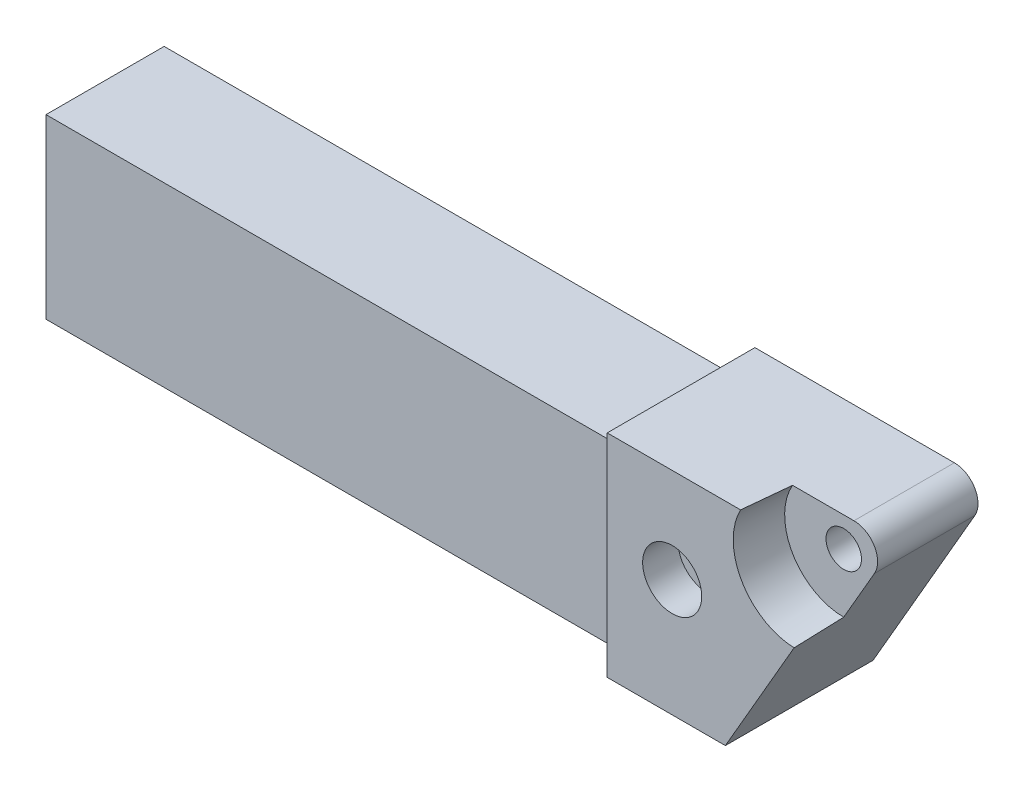
SolidWorks part; units mm, degrees
ref_plane "前视基准面" through (0, 0, 0) normal (0, 0, 1) x (1, 0, 0)
ref_plane "上视基准面" through (0, 0, 0) normal (0, 1, 0) x (1, 0, 0)
ref_plane "右视基准面" through (0, 0, 0) normal (1, 0, 0) x (0, 0, -1)
sketch "草图1" plane through (0, 0, 0) normal (0, 0, 1) x (1, 0, 0)
  line L1 (-50, 15) -> (50, 15)
  line L2 (-50, 15) -> (-50, -15)
  line L3 (-50, -15) -> (50, -15)
  line L4 (50, 15) -> (50, -15)
  line L5 (-50, 15) -> (50, -15) construction
  line L6 (-50, -15) -> (50, 15) construction
  point P0 (0, 0)
  dimension "D1" = 100
  dimension "D2" = 30
extrude "凸台-拉伸1" add sketch "草图1" along normal blind 20
sketch "草图2" plane through (0, 0, 20) normal (0, 0, 1) x (1, 0, 0)
  line L0 (50, -15) -> (70, -15)
  line L1 (70, -15) -> (90.6951, 20.845)
  line L2 (90.6951, 20.845) -> (50, 20.845)
  line L3 (50, 20.845) -> (50, -15)
  dimension "D1" = 60
  dimension "D2" = 20
extrude "凸台-拉伸2" add sketch "草图2" along normal blind 5 and the other way blind 20
fillet "圆角1" radius 5 2 edges
sketch "草图3" plane through (0, 0, 25) normal (0, 0, 1) x (1, 0, 0)
  line L0 (90.6951, 20.845) -> (57.2845, 1.5554) construction
  line L1 (90.6951, 20.845) -> (50, 20.845) construction
  circle A0 centre (82.0349, 15.845) radius 10
  dimension "D2" = 20
  dimension "D1" = 30
extrude "切除-拉伸1" cut sketch "草图3" against normal blind 8
sketch "草图4" plane through (0, 0, 17) normal (0, 0, 1) x (1, 0, 0)
  line L0 (90.6951, 20.845) -> (79.4368, 14.345) construction
  circle A0 centre (82.0349, 15.845) radius 3
  dimension "D1" = 6
  dimension "D2" = 10
extrude "切除-拉伸2" cut sketch "草图4" against normal through all
cosmetic thread "装饰螺纹线1" parameters "D2"=9
hole_wizard "孔1" positions "3D草图1" profile "草图6" legacy
sketch3d "3D草图1"
  line L0 (50, 20, 25) -> (50, -15, 25) construction
  line L1 (73.3746, 20.845, 25) -> (50, 20.845, 25) construction
  point P0 (61, 4.845, 25)
  dimension "D1" = 11
  dimension "D2" = 16
sketch "草图6" plane through (61, 4.845, 25) normal (1, 0, 0) x (0, -1, 0)
  line L0 (0, 0) -> (0, 25)
  line L1 (0, 25) -> (2.5, 25)
  line L2 (2.5, 25) -> (2.5, 6)
  line L3 (2.5, 6) -> (5, 6)
  line L4 (5, 6) -> (5, 0)
  line L5 (5, 0) -> (0, 0)
  line L6 (0, 110) -> (0, -10) construction
  dimension "直径" = 5
  dimension "深度" = 25
  dimension "柱坑直径" = 10
  dimension "柱坑深度" = 6
cosmetic thread "装饰螺纹线2" parameters "D2"=24
draft "拔模1" type of draft neutral plane draft angle 5 faces to draft 1 face at (75.5397, 12.095, 21) neutral plane through (82.0349, 15.845, 17) neutral plane normal (0, 0, 1) parameters "D1"=5
fillet "圆角2" radius 4 1 edges at (90.6951, 20.845, 8.5)
